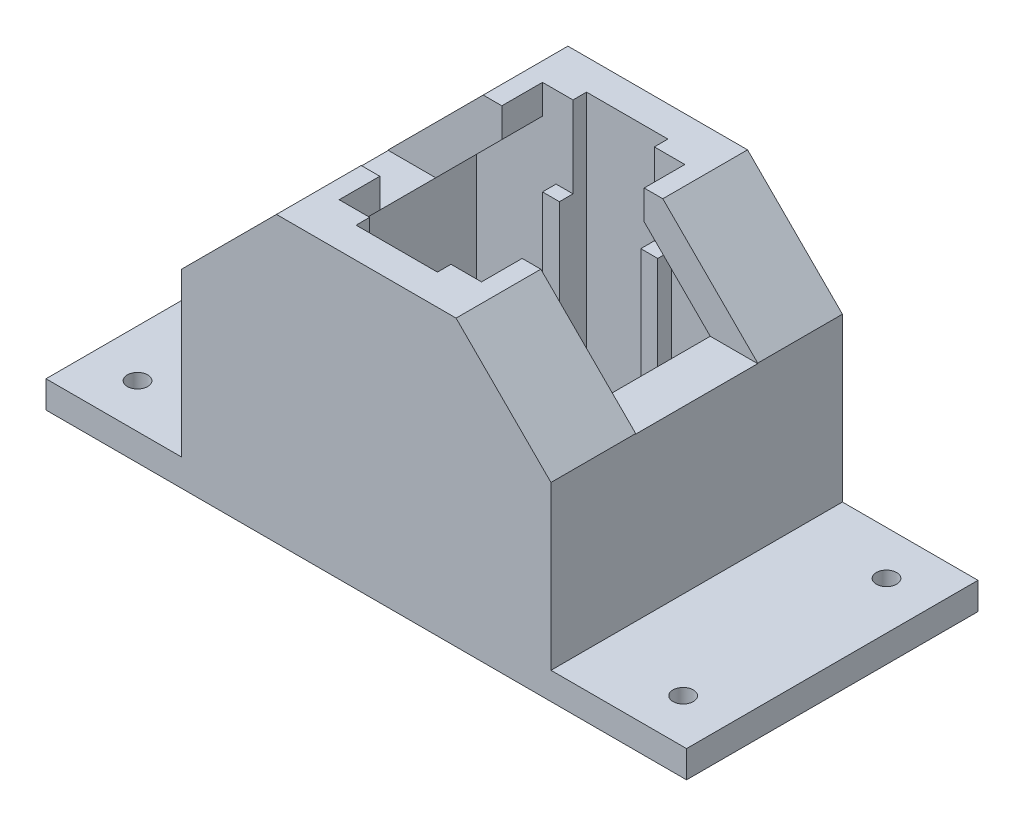
SolidWorks part; units mm, degrees
ref_plane "Płaszczyzna przednia" through (0, 0, 0) normal (0, 0, 1) x (1, 0, 0)
ref_plane "Płaszczyzna górna" through (0, 0, 0) normal (0, 1, 0) x (1, 0, 0)
ref_plane "Płaszczyzna prawa" through (0, 0, 0) normal (1, 0, 0) x (0, 0, -1)
sketch "Sketch1" plane through (0, 0, 0) normal (0, 1, 0) x (1, 0, 0)
  line L0 (0, 19.4294) -> (0, -20.6549) construction
  line L1 (-20.25, 15) -> (20.25, 15)
  line L2 (-20.25, 15) -> (-20.25, -15)
  line L3 (-20.25, -15) -> (20.25, -15)
  line L4 (20.25, 15) -> (20.25, -15)
  line L5 (-20.25, 15) -> (20.25, -15) construction
  line L6 (-20.25, -15) -> (20.25, 15) construction
  line L7 (-32.8665, 0) -> (32.8665, 0) construction
  line L8 (8.5, 13) -> (6, 13)
  line L9 (-8.5, 15) -> (-6, 15)
  line L10 (-8.5, 15) -> (-8.5, 13)
  line L11 (-8.5, 13) -> (-6, 13)
  line L12 (-6, 15) -> (-6, 13)
  line L13 (6, 15) -> (6, 13)
  line L14 (8.5, 15) -> (6, 15)
  line L15 (8.5, 15) -> (8.5, 13)
  line L16 (8.5, -15) -> (8.5, -13)
  line L17 (8.5, -15) -> (6, -15)
  line L18 (6, -15) -> (6, -13)
  line L19 (8.5, -13) -> (6, -13)
  line L20 (-8.5, -13) -> (-6, -13)
  line L21 (-6, -15) -> (-6, -13)
  line L22 (-8.5, -15) -> (-6, -15)
  line L23 (-8.5, -15) -> (-8.5, -13)
  line L24 (-27.25, 22) -> (-27.25, -22)
  line L25 (-27.25, -22) -> (27.25, -22)
  line L26 (27.25, 22) -> (27.25, -22)
  line L27 (-27.25, 22) -> (27.25, 22)
  point P0 (0, 0)
  point P10 (0, 15)
  dimension "D1" = 30
  dimension "D2" = 40.5
  dimension "D3" = 2.5
  dimension "D4" = 2
  dimension "D5" = 6
  dimension "1" = 7
extrude "Boss-Extrude1" add sketch "Sketch1" along normal blind 42 contours L15 L1 L13 L8 | L27 L24 L25 L26 L22 L23 L3 L2 L1 L4 L21 | L11 L12 L9 L10 | L20 L21 L22 L23 | L19 L18 L17 L16 region at (7.25, 0, -14) region at (0, 0, -21.2996)
chamfer "Chamfer2" distance 14 angle 45 2 edges at (27.25, 42, 0) (-27.25, 42, 0)
chamfer "Chamfer3" distance 10 angle 45 2 edges at (20.25, 35, 0) (-20.25, 35, 0) first distance on face at (18.5, 36.75, 0) first distance on face at (-18.5, 36.75, 0)
sketch "Sketch2" plane through (0, 0, -15) normal (0, 0, 1) x (1, 0, 0)
  line L1 (-27.25, 20.9289) -> (-6.1789, 42)
  line L3 (-27.25, 28) -> (-27.25, 27.9289) construction
  line L8 (0, 51.2829) -> (0, -13.1032) construction
  line L9 (-6, 42) -> (6, 42) construction
  line L12 (-27.25, 28) -> (-13.25, 42)
  line L13 (-13.25, 42) -> (-6.1789, 42)
  line L14 (-13.25, 42) -> (-27.25, 28) construction
  line L15 (-27.25, 28) -> (-27.25, 20.9289)
  line L16 (13.25, 42) -> (6.1789, 42)
  line L17 (27.25, 28) -> (13.25, 42)
  line L18 (27.25, 28) -> (27.25, 20.9289)
  line L19 (27.25, 20.9289) -> (6.1789, 42)
  dimension "D1" = 5
extrude "Boss-Extrude2" add sketch "Sketch2" along normal blind 6
ref_plane "Plane1" through (0, 0, 0) normal (0, 0, 1) x (1, 0, 0)
mirror "Mirror2" about plane through (0, 0, 0) normal (0, 0, 1) of "Boss-Extrude2"
sketch "Sketch4" plane through (0, 0, 0) normal (0, -1, 0) x (1, 0, 0)
  line L0 (0, 30.4744) -> (0, -31.4814) construction
  line L1 (27.25, 22) -> (47.25, 22)
  line L2 (27.25, 22) -> (27.25, -22)
  line L3 (27.25, -22) -> (47.25, -22)
  line L4 (47.25, 22) -> (47.25, -22)
  line L5 (-27.25, -22) -> (-47.25, -22)
  line L6 (-47.25, 22) -> (-47.25, -22)
  line L7 (-27.25, 22) -> (-47.25, 22)
  line L8 (-27.25, 22) -> (-27.25, -22)
  line L9 (-55.8577, 0) -> (55.4548, 0) construction
  circle A0 centre (40.25, 15) radius 1.5
  circle A1 centre (40.25, -15) radius 1.5
  circle A2 centre (-40.25, -15) radius 1.5
  circle A3 centre (-40.25, 15) radius 1.5
  dimension "D2" = 3
  dimension "D1" = 20
  dimension "D3" = 7
  dimension "D4" = 7
extrude "Boss-Extrude3" add sketch "Sketch4" against normal blind 4
sketch "Sketch5" plane through (0, 42, 0) normal (0, 1, 0) x (1, 0, 0)
  line L0 (0, 26.9268) -> (0, -15) construction
  line L1 (-10.5, 15) -> (10.5, 15)
  line L2 (-10.5, 15) -> (-10.5, -15)
  line L3 (-10.5, -15) -> (10.5, -15)
  line L4 (10.5, 15) -> (10.5, -15)
  line L7 (20.25, -15) -> (8.5, -15) construction
  line L8 (-6, 15) -> (6, 15) construction
  dimension "D1" = 21
extrude "Cut-Extrude1" cut sketch "Sketch5" against normal blind 12
sketch "Sketch6" plane through (0, 0, 15) normal (0, 0, -1) x (-1, 0, 0)
  line L0 (10.5, 42) -> (-10.5, 42) construction
  line L1 (-6, 42) -> (6, 42)
  line L2 (-6, 42) -> (-6, 0)
  line L3 (-6, 0) -> (6, 0)
  line L4 (6, 42) -> (6, 0)
extrude "Cut-Extrude2" cut sketch "Sketch6" against normal blind 2
mirror "Mirror3" about plane through (0, 0, 0) normal (0, 0, 1) of "Cut-Extrude2"
sketch "Sketch7" plane through (0, 0, -22) normal (0, 0, -1) x (-1, 0, 0)
  line L10 (13.25, 42) -> (-13.25, 42)
  line L11 (-13.25, 42) -> (-27.25, 28)
  line L12 (-27.25, 28) -> (-27.25, 4)
  line L13 (-27.25, 4) -> (-47.25, 4)
  line L14 (-47.25, 4) -> (-47.25, 0)
  line L15 (-47.25, 0) -> (47.25, 0)
  line L16 (47.25, 0) -> (47.25, 4)
  line L17 (47.25, 4) -> (27.25, 4)
  line L18 (27.25, 4) -> (27.25, 28)
  line L19 (27.25, 28) -> (13.25, 42)
  line L20 (13.25, 42) -> (-13.25, 42)
  line L21 (-13.25, 42) -> (-27.25, 28)
  line L22 (-27.25, 28) -> (-27.25, 4)
  line L23 (-27.25, 4) -> (-47.25, 4)
  line L24 (-47.25, 4) -> (-47.25, 0)
  line L25 (-47.25, 0) -> (47.25, 0)
  line L26 (47.25, 0) -> (47.25, 4)
  line L27 (47.25, 4) -> (27.25, 4)
  line L28 (27.25, 4) -> (27.25, 28)
  line L29 (27.25, 28) -> (13.25, 42)
  dimension "D1" = 0
extrude "Cut-Extrude3" cut sketch "Sketch7" against normal blind 0.5
sketch "Sketch8" plane through (0, 0, 22) normal (0, 0, 1) x (1, 0, 0)
  line L10 (27.25, 4) -> (27.25, 28)
  line L11 (27.25, 28) -> (13.25, 42)
  line L12 (13.25, 42) -> (-13.25, 42)
  line L13 (-13.25, 42) -> (-27.25, 28)
  line L14 (-27.25, 28) -> (-27.25, 4)
  line L15 (-27.25, 4) -> (-47.25, 4)
  line L16 (-47.25, 4) -> (-47.25, 0)
  line L17 (-47.25, 0) -> (47.25, 0)
  line L18 (47.25, 0) -> (47.25, 4)
  line L19 (47.25, 4) -> (27.25, 4)
  line L20 (27.25, 4) -> (27.25, 28)
  line L21 (27.25, 28) -> (13.25, 42)
  line L22 (13.25, 42) -> (-13.25, 42)
  line L23 (-13.25, 42) -> (-27.25, 28)
  line L24 (-27.25, 28) -> (-27.25, 4)
  line L25 (-27.25, 4) -> (-47.25, 4)
  line L26 (-47.25, 4) -> (-47.25, 0)
  line L27 (-47.25, 0) -> (47.25, 0)
  line L28 (47.25, 0) -> (47.25, 4)
  line L29 (47.25, 4) -> (27.25, 4)
  dimension "D1" = 0
extrude "Cut-Extrude4" cut sketch "Sketch8" against normal blind 0.5
